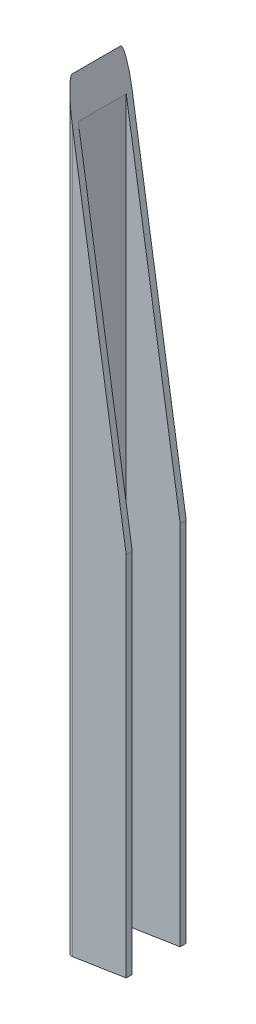
SolidWorks part; units mm, degrees
ref_plane "Спереди" through (0, 0, 0) normal (0, 0, 1) x (1, 0, 0)
ref_plane "Сверху" through (0, 0, 0) normal (0, 1, 0) x (1, 0, 0)
ref_plane "Справа" through (0, 0, 0) normal (1, 0, 0) x (0, 0, -1)
sketch "Эскиз1" plane through (0, 0, 0) normal (0, 1, 0) x (1, 0, 0)
  line L1 (-37, 15) -> (37, 15)
  line L2 (-40, 12) -> (-40, -12)
  line L3 (-37, -15) -> (37, -15)
  line L4 (40, 12) -> (40, -12)
  line L5 (-40, 15) -> (40, -15) construction
  line L6 (-40, -15) -> (40, 15) construction
  arc A0 (-37, 15) -> (-40, 12) centre (-37, 12) ccw
  arc A1 (-40, -12) -> (-37, -15) centre (-37, -12) ccw
  arc A2 (37, -15) -> (40, -12) centre (37, -12) ccw
  arc A3 (37, 15) -> (40, 12) centre (37, 12) cw
  point P0 (0, 0)
  dimension "D1" = 3
extrude "Вытянуть-Тонкостенный1" add sketch "Эскиз1" along normal blind 380 thin thin type one direction reverse wall 3
sketch "Эскиз2" plane through (0, 380, 0) normal (0, 1, 0) x (1, 0, 0)
  line L1 (-10, -21.9251) -> (41.1465, -21.9251)
  line L2 (-10, -21.9251) -> (-10, 20.9728)
  line L3 (-10, 20.9728) -> (41.1465, 20.9728)
  line L4 (41.1465, -21.9251) -> (41.1465, 20.9728)
  point P4 (-14.9462, -21.7564)
  point P5 (-23.465, -21.9251)
  point P6 (0, 0)
extrude "Вырез-Вытянуть1" cut sketch "Эскиз2" against normal through all
sketch "Эскиз3" plane through (0, 0, 15) normal (0, 0, 1) x (1, 0, 0)
  line L0 (-40, 380) -> (-10, 188.0753)
  line L1 (-10, 0) -> (-10, 380) construction
  line L2 (-10, 188.0753) -> (-10, 4.6893)
  line L3 (-10, 4.6893) -> (-40, 0)
  line L4 (-40, 0) -> (-40, 380)
  line L5 (67.3818, 16.785) -> (-80.8186, -6.3804) construction
  line L6 (-10, 380) -> (-10, 0) construction
  point P5 (-6.0286, 171.752)
  point P9 (0, 0)
  point P14 (-6.0286, 188.0753)
extrude "Вырез-Вытянуть2" cut sketch "Эскиз3" against normal through all flip side to cut
